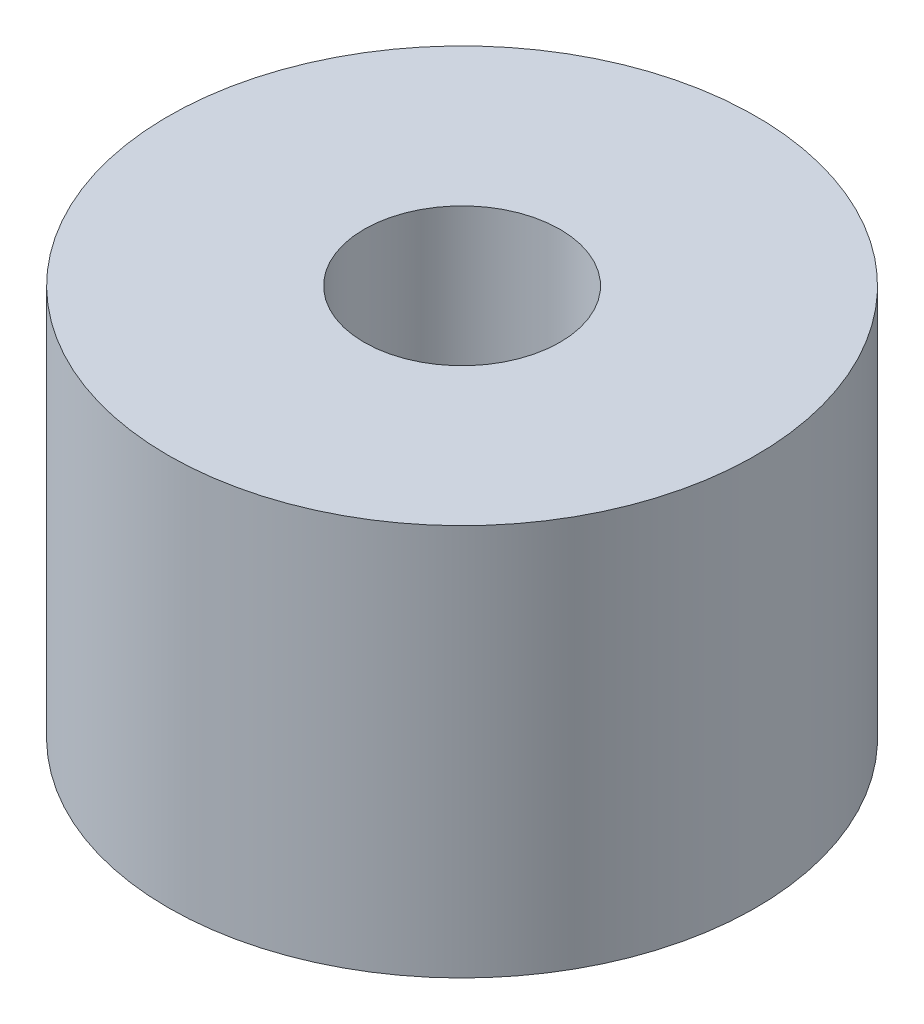
SolidWorks part; units mm, degrees
ref_plane "Front" through (0, 0, 0) normal (0, 0, 1) x (1, 0, 0)
ref_plane "Top" through (0, 0, 0) normal (0, 1, 0) x (1, 0, 0)
ref_plane "Right" through (0, 0, 0) normal (1, 0, 0) x (0, 0, -1)
sketch "Sketch1" plane through (0, 0, 0) normal (0, 1, 0) x (1, 0, 0)
  circle A0 centre (0, 0) radius 1.5875
  circle A1 centre (0, 0) radius 4.7625
  dimension "D1" = 3.175
  dimension "D2" = 3.175
extrude "Boss-Extrude1" add sketch "Sketch1" along normal blind 6.35
